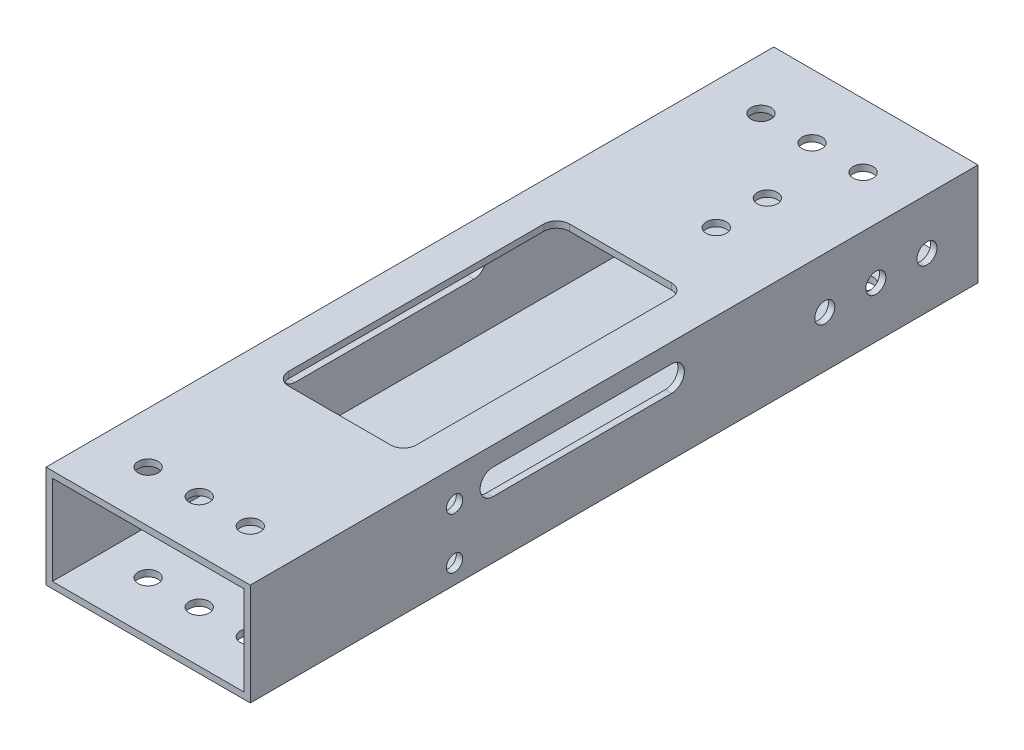
SolidWorks part; units mm, degrees
other "Markup4"
sketch "Sketch7" plane through (25.4, -12.7, 0) normal (0.9921, -0.1226, -0.0275) x (-0.1217, -0.992, 0.0335)
other "Markup5"
sketch "Sketch10"
material "6061-T6 (SS)"
ref_plane "Front Plane" through (0, 0, 0) normal (0, 0, 1) x (1, 0, 0)
ref_plane "Top Plane" through (0, 0, 0) normal (0, 1, 0) x (1, 0, 0)
ref_plane "Right Plane" through (0, 0, 0) normal (1, 0, 0) x (0, 0, -1)
sketch "Sketch1" plane through (0, 0, 0) normal (0, 0, 1) x (1, 0, 0)
  line L1 (-25.4, -12.7) -> (25.4, -12.7)
  line L2 (-25.4, -12.7) -> (-25.4, 12.7)
  line L3 (-25.4, 12.7) -> (25.4, 12.7)
  line L4 (25.4, -12.7) -> (25.4, 12.7)
  line L5 (-25.4, -12.7) -> (25.4, 12.7) construction
  line L6 (-25.4, 12.7) -> (25.4, -12.7) construction
  line L7 (-23.8125, -11.1125) -> (23.8125, -11.1125)
  line L8 (-23.8125, -11.1125) -> (-23.8125, 11.1125)
  line L9 (-23.8125, 11.1125) -> (23.8125, 11.1125)
  line L10 (23.8125, -11.1125) -> (23.8125, 11.1125)
  line L11 (-23.8125, -11.1125) -> (23.8125, 11.1125) construction
  line L12 (-23.8125, 11.1125) -> (23.8125, -11.1125) construction
  point P0 (0, 0)
  point P6 (0, 0)
  dimension "D1" = 50.8
  dimension "D2" = 25.4
  dimension "D3" = 1.5875
  dimension "D4" = 1.5875
extrude "Boss-Extrude1" add sketch "Sketch1" along normal blind 180.975
sketch "Sketch2" plane through (0, 12.7, 0) normal (0, 1, 0) x (1, 0, 0)
  line L0 (25.4, 0) -> (-25.4, 0) construction
  line L1 (-25.4, -180.975) -> (-25.4, 0) construction
  line L3 (25.4, -180.975) -> (-25.4, -180.975) construction
  circle A0 centre (-12.7, -15.875) radius 2.4892
  circle A1 centre (0, -15.875) radius 2.4892
  circle A2 centre (12.7, -15.875) radius 2.4892
  circle A3 centre (-12.7, -168.275) radius 2.4892
  circle A4 centre (0, -168.275) radius 2.4892
  circle A5 centre (12.7, -168.275) radius 2.4892
  circle A6 centre (6.35, -33.3375) radius 2.4892
  circle A7 centre (6.35, -46.0375) radius 2.4892
  dimension "D1" = 4.9784
  dimension "D2" = 15.875
  dimension "D3" = 12.7
  dimension "D4" = 12.7
  dimension "D5" = 12.7
  dimension "D6" = 12.7
  dimension "D7" = 31.75
  dimension "D8" = 33.3375
extrude "Cut-Extrude1" cut sketch "Sketch2" against normal through all
sketch "Sketch9" plane through (0, 12.7, 0) normal (0, 1, 0) x (1, 0, 0)
  line L0 (25.4, 0) -> (-25.4, 0) construction
  line L1 (-15.875, -63.5) -> (15.875, -63.5)
  line L2 (-15.875, -63.5) -> (-15.875, -133.35)
  line L3 (-15.875, -133.35) -> (15.875, -133.35)
  line L4 (15.875, -63.5) -> (15.875, -133.35)
  line L5 (-25.4, -180.975) -> (-25.4, 0) construction
  dimension "D1" = 63.5
  dimension "D2" = 31.75
  dimension "D3" = 9.525
  dimension "D4" = 69.85
extrude "Cut-Extrude2" cut sketch "Sketch9" against normal up to surface (23.8125 mm away) up to face at (0, -11.1125, 18.3642)
fillet "Fillet1" radius 3.175 4 edges at (-15.875, 11.9062, 63.5) (15.875, 11.9062, 133.35) (-15.875, 11.9062, 133.35) (15.875, 11.9062, 63.5)
sketch "Sketch11" plane through (0, 0, 0) normal (1, 0, 0) x (0, 0, -1)
  line L0 (-120.65, 4.7625) -> (-76.2, 4.7625) construction
  line L1 (-120.65, 7.9375) -> (-76.2, 7.9375)
  line L2 (-120.65, 1.5875) -> (-76.2, 1.5875)
  line L3 (-130.175, 12.7) -> (-66.675, 12.7) construction
  line L4 (-180.975, 12.7) -> (0, 12.7) construction
  line L5 (0, -12.7) -> (0, 12.7) construction
  arc A0 (-120.65, 7.9375) -> (-120.65, 1.5875) centre (-120.65, 4.7625) ccw
  arc A1 (-76.2, 1.5875) -> (-76.2, 7.9375) centre (-76.2, 4.7625) ccw
  circle A2 centre (-130.175, 4.7625) radius 2.0193
  circle A3 centre (-130.175, -7.9375) radius 2.0193
  circle A4 centre (-98.425, 4.7625) radius 9.525 construction
  circle A5 centre (-12.7, 0) radius 2.4892
  circle A6 centre (-25.4, 0) radius 2.4892
  circle A7 centre (-38.1, 0) radius 2.4892
  point P2 (-98.425, 4.7625)
  point P10 (-98.425, 12.7)
  point P26 (-38.1, -0.2273)
  point P27 (0, 0)
  point P29 (0, 0)
  point P30 (0, 0)
  point P31 (-25.4, 0)
  point P32 (0, 0)
  dimension "D1" = 3.175
  dimension "D4" = 4.0386
  dimension "D6" = 19.05
  dimension "D8" = 4.9784
  dimension "D9" = 12.7
  dimension "D10" = 12.7
  dimension "D11" = 12.7
  dimension "D2" = 44.45
  dimension "D3" = 7.9375
  dimension "D5" = 9.525
  dimension "D7" = 12.7
extrude "Cut-Extrude3" cut sketch "Sketch11" against normal through all both and the other way through all
